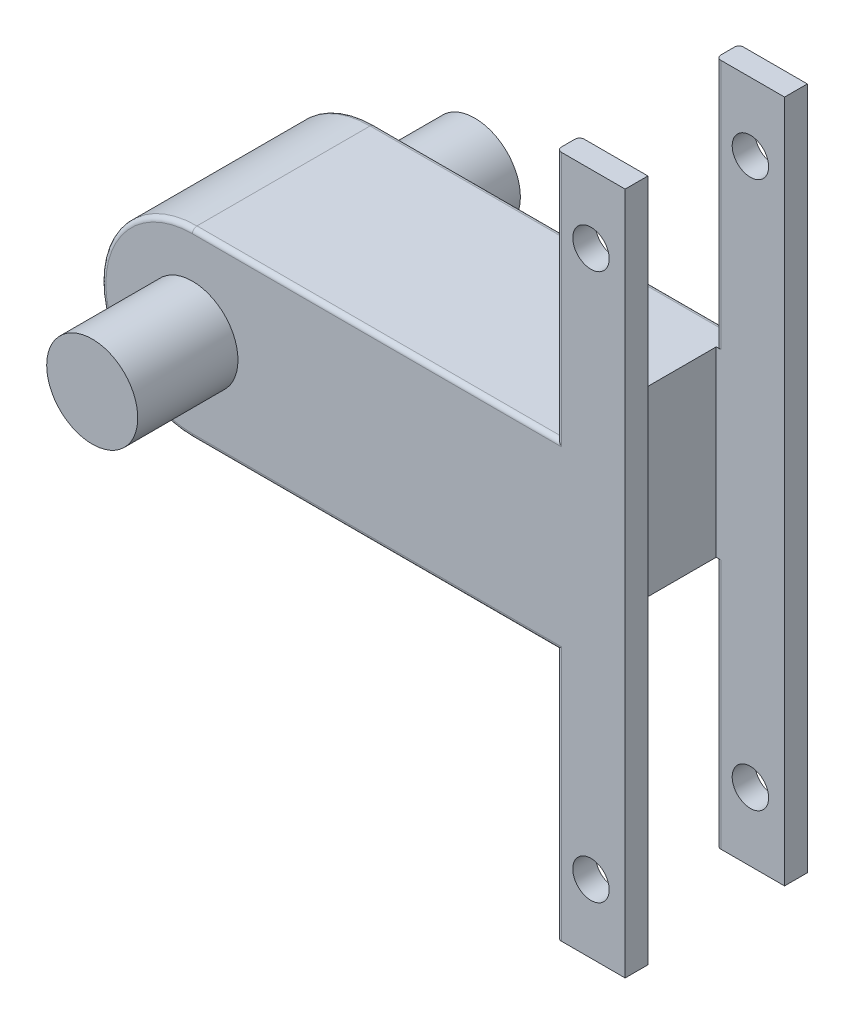
SolidWorks part; units mm, degrees
ref_plane "Front Plane" through (0, 0, 0) normal (0, 0, 1) x (1, 0, 0)
ref_plane "Top Plane" through (0, 0, 0) normal (0, 1, 0) x (1, 0, 0)
ref_plane "Right Plane" through (0, 0, 0) normal (1, 0, 0) x (0, 0, -1)
sketch "Sketch1" plane through (0, 0, 0) normal (0, 0, 1) x (1, 0, 0)
  line L1 (0, 75) -> (0, 20)
  line L2 (0, 75) -> (15, 75)
  line L3 (15, 75) -> (15, -75)
  line L4 (15, -75) -> (0, -75)
  line L5 (-80, 20) -> (0, 20)
  line L6 (-80, -20) -> (0, -20)
  line L7 (0, -20) -> (0, -75)
  arc A0 (-80, 20) -> (-80, -20) centre (-80, 0) ccw
  circle A1 centre (7.5, 60) radius 4
  circle A2 centre (7.5, -60) radius 4
  point P7 (0, 0)
  point P15 (7.5, -75)
  dimension "D2" = 40
  dimension "D1" = 8
  dimension "D6" = 8
  dimension "D3" = 150
  dimension "D4" = 15
  dimension "D5" = 15
  dimension "D7" = 15
extrude "Boss-Extrude1" add sketch "Sketch1" along normal blind 40
sketch "Sketch2" plane through (0, 0, 0) normal (0, 0, -1) x (-1, 0, 0)
  circle A0 centre (80, 0) radius 10
  dimension "D1" = 20
extrude "Boss-Extrude2" add sketch "Sketch2" along normal blind 22
ref_plane "Plane1" through (0, 0, 20) normal (0, 0, 1) x (1, 0, 0)
mirror "Mirror1" about plane through (0, 0, 20) normal (0, 0, 1) of "Boss-Extrude2"
sketch "Sketch3" plane through (0, 75, 0) normal (0, 1, 0) x (1, 0, 0)
  line L0 (15, -20) -> (0, -20) construction
  line L1 (15, -40) -> (15, 0) construction
  line L2 (0, -40) -> (0, 0) construction
  line L3 (0, -40) -> (0, 0) construction
  line L4 (15, -5) -> (0, -5)
  line L5 (15, -5) -> (15, -35)
  line L6 (15, -35) -> (0, -35)
  line L7 (0, -5) -> (0, -35)
  line L8 (15, -5) -> (0, -35) construction
  line L9 (15, -35) -> (0, -5) construction
  point P6 (7.5, -20)
  dimension "D1" = 30
extrude "Cut-Extrude1" cut sketch "Sketch3" against normal blind 150
fillet "Fillet1" radius 1 14 edges at (-40, -20, 0) (-100, 0, 0) (-40, -20, 40) (-100, 0, 40) (0, -47.5, 0) (0, -47.5, 5) (0, -47.5, 35) (0, -47.5, 40) (0, 47.5, 40) (0, 47.5, 35) (0, 47.5, 5) (0, 47.5, 0) (-40, 20, 0) (-40, 20, 40)
